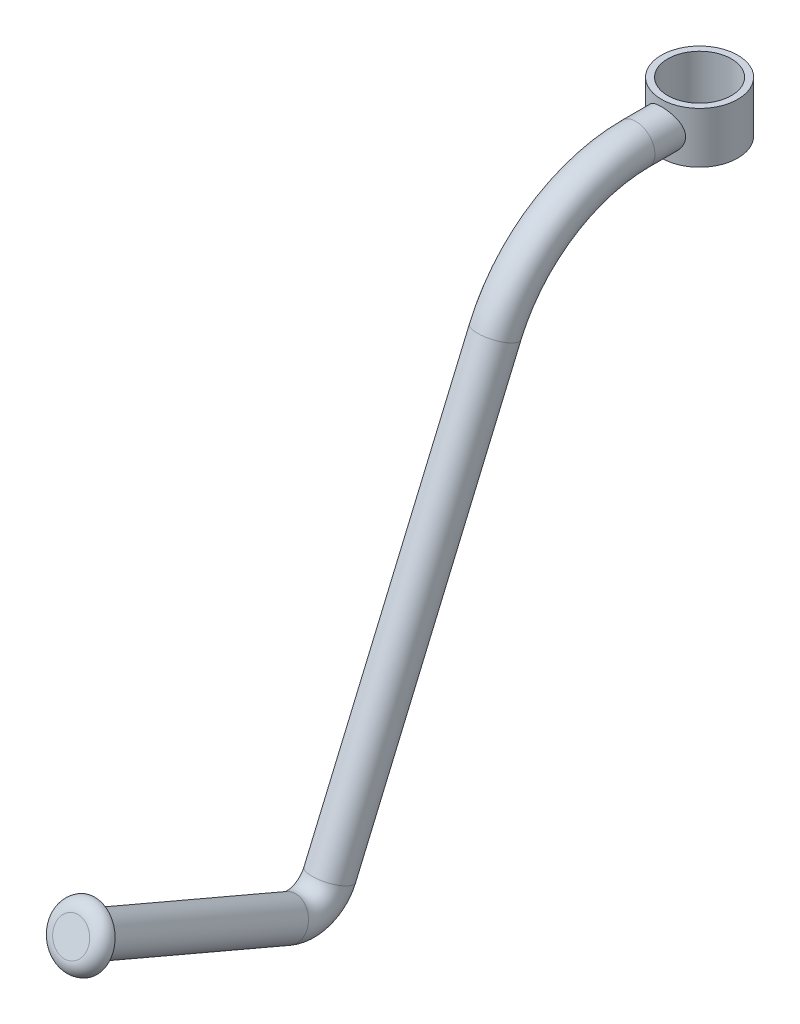
SolidWorks part; units mm, degrees
ref_plane "Front Plane" through (0, 0, 0) normal (0, 0, 1) x (1, 0, 0)
ref_plane "Top Plane" through (0, 0, 0) normal (0, 1, 0) x (1, 0, 0)
ref_plane "Right Plane" through (0, 0, 0) normal (1, 0, 0) x (0, 0, -1)
sketch "Sketch1" plane through (0, 0, 0) normal (1, 0, 0) x (0, 0, -1)
  line L0 (-21.7612, 0) -> (-25.4018, 0) construction
  line L1 (-164.0804, -198.2141) -> (-245.8429, -163.3129)
  line L3 (0, 0) -> (-25.4018, 0)
  line L4 (-81.4675, -37.0277) -> (-147.4141, -191.5196)
  arc A0 (-25.4018, 0) -> (-81.4675, -37.0277) centre (-25.4018, -60.96) ccw
  arc A1 (-147.4141, -191.5196) -> (-164.0804, -198.2141) centre (-159.0945, -186.5337) cw
  point P7 (-58.6767, 0)
  point P11 (-65.6619, 0)
  dimension "D1" = 12.7
  dimension "D3" = 60.96
sketch "Sketch2" plane through (0, 0, 0) normal (0, 0, 1) x (1, 0, 0)
  circle A0 centre (0, 0) radius 7.62
sweep "Sweep1" add profiles "Sketch2" path "Sketch1"
sketch "Sketch4" plane through (0, 63.5957, 148.9845) normal (0, 0.3926, 0.9197) x (1, 0, 0)
  circle A0 centre (0, -246.7165) radius 11.9503
extrude "Boss-Extrude1" add sketch "Sketch4" along normal blind 5.08
fillet "Fillet1" radius 5.08 1 edges at (0, -172.3094, 255.2066)
sketch "Sketch5" plane through (0, 0, 0) normal (0, 1, 0) x (1, 0, 0)
  circle A0 centre (0, 0) radius 15.24
extrude "Boss-Extrude2" add sketch "Sketch5" along normal blind 10.16 and the other way blind 10.16
sketch "Sketch6" plane through (0, 10.16, 0) normal (0, 1, 0) x (1, 0, 0)
  circle A0 centre (0, 0) radius 12.7
extrude "Cut-Extrude1" cut sketch "Sketch6" against normal through all
